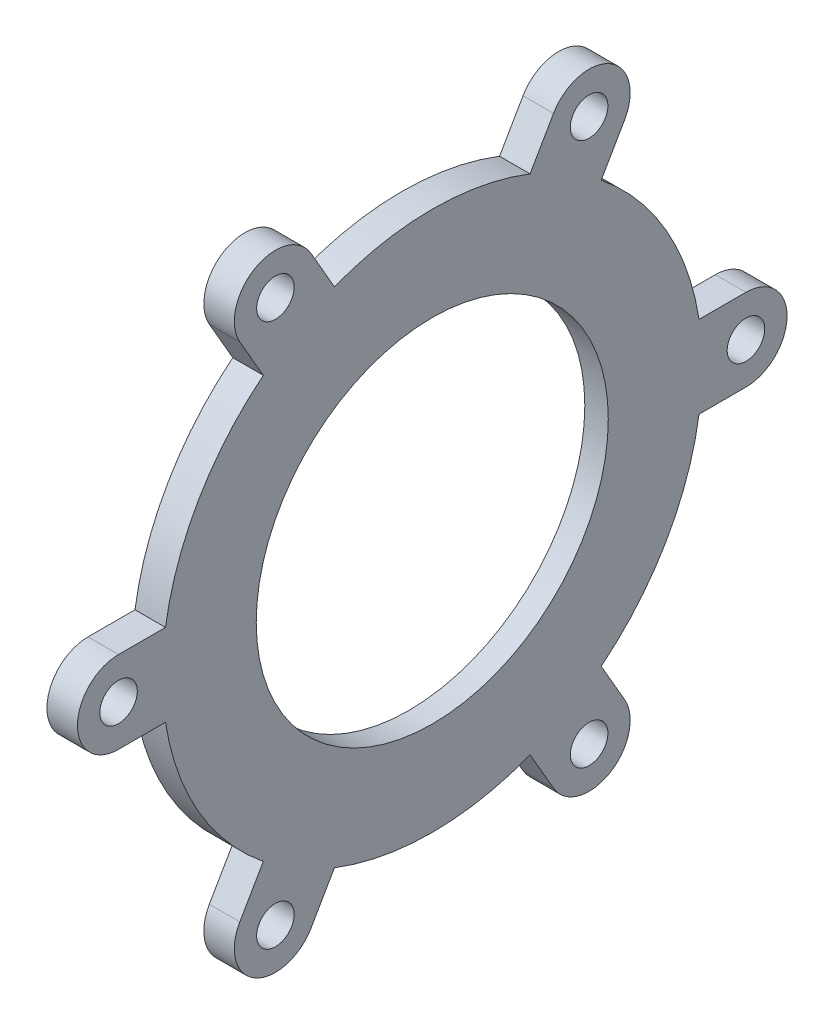
SolidWorks part; units mm, degrees
ref_plane "Front Plane" through (0, 0, 0) normal (0, 0, 1) x (1, 0, 0)
ref_plane "Top Plane" through (0, 0, 0) normal (0, 1, 0) x (1, 0, 0)
ref_plane "Right Plane" through (0, 0, 0) normal (1, 0, 0) x (0, 0, -1)
sketch "Sketch2" plane through (0, 0, 0) normal (1, 0, 0) x (0, 0, -1)
  line L0 (113.6607, 17.5) -> (133.6607, 17.5)
  line L2 (113.6607, -17.5) -> (133.6607, -17.5)
  line L3 (71.9858, -89.683) -> (81.9858, -107.0035)
  line L4 (41.6749, -107.183) -> (51.6749, -124.5035)
  line L5 (-41.6749, -107.183) -> (-51.6749, -124.5035)
  line L6 (-71.9858, -89.683) -> (-81.9858, -107.0035)
  line L7 (-113.6607, -17.5) -> (-133.6607, -17.5)
  line L8 (-113.6607, 17.5) -> (-133.6607, 17.5)
  line L9 (-71.9858, 89.683) -> (-81.9858, 107.0035)
  line L10 (-41.6749, 107.183) -> (-51.6749, 124.5035)
  line L11 (41.6749, 107.183) -> (51.6749, 124.5035)
  line L12 (71.9858, 89.683) -> (81.9858, 107.0035)
  circle A0 centre (0, 0) radius 95
  circle A1 centre (0, 0) radius 115
  arc A2 (133.6607, 17.5) -> (133.6607, -17.5) centre (133.6607, 0) cw
  circle A3 centre (133.6607, 0) radius 8
  arc A4 (81.9858, -107.0035) -> (51.6749, -124.5035) centre (66.8303, -115.7535) cw
  circle A5 centre (66.8303, -115.7535) radius 8
  arc A6 (-51.6749, -124.5035) -> (-81.9858, -107.0035) centre (-66.8303, -115.7535) cw
  circle A7 centre (-66.8303, -115.7535) radius 8
  arc A8 (-133.6607, -17.5) -> (-133.6607, 17.5) centre (-133.6607, 0) cw
  circle A9 centre (-133.6607, 0) radius 8
  arc A10 (-81.9858, 107.0035) -> (-51.6749, 124.5035) centre (-66.8303, 115.7535) cw
  circle A11 centre (-66.8303, 115.7535) radius 8
  arc A12 (51.6749, 124.5035) -> (81.9858, 107.0035) centre (66.8303, 115.7535) cw
  circle A13 centre (66.8303, 115.7535) radius 8
  circle A14 centre (0, 0) radius 75
  point P45 (0, 0)
  dimension "D1" = 190
  dimension "D3" = 20
  dimension "D5" = 16
  dimension "D7" = 150
  dimension "D4" = 35
  dimension "D2" = 20
  dimension "D6" = 6
extrude "Boss-Extrude1" add sketch "Sketch2" along normal blind 10 contours A0 A14 | A1 A0 | A8 L7 A1 L8 A9 | A10 L9 A1 L10 A11 | A12 L11 A1 L12 A13 | A2 L0 A1 L2 A3 | A4 L3 A1 L4 A5 | A6 L5 A1 L6 A7 region at (0, 16.987, -123.6607) region at (0, 8.5274, -111.4215) region at (0, 100.121, -57.8049) region at (0, -98.6482, -76.4577) region at (0, 100.121, 57.8049) region at (0, -115.5384, 47.2029) region at (0, 0, 115.513) region at (0, 0, 92.313)
extrude "Boss-Extrude2" add sketch "Sketch2<5>" against normal blind 3 contours A1 A0 | A2 L0 A1 L2 A3 | A12 L11 A1 L12 A13 | A10 L9 A1 L10 A11 | A8 L7 A1 L8 A9 | A6 L5 A1 L6 A7 | A4 L3 A1 L4 A5 region at (0, 16.987, -123.6607) region at (0, 8.5274, -111.4215) region at (0, 100.121, -57.8049) region at (0, -98.6482, -76.4577) region at (0, 100.121, 57.8049) region at (0, -115.5384, 47.2029) region at (0, 0, 115.513)
sketch "Sketch2<5>" plane through (0, 0, 0) normal (1, 0, 0) x (0, 0, -1) same geometry as "Sketch2"
fillet "Fillet1" radius 2.5 1 edges at (0, 0, -95)
